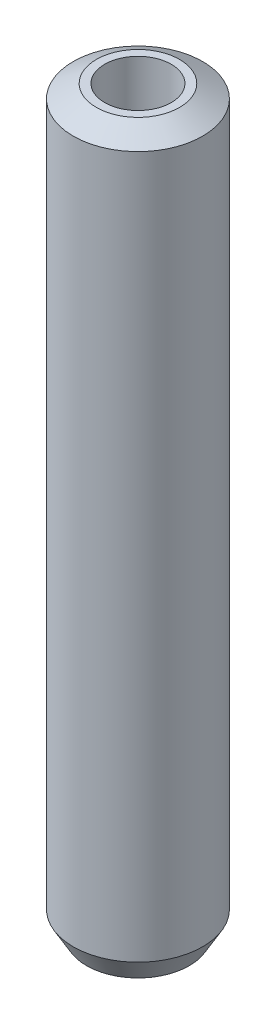
SolidWorks part; units mm, degrees
ref_plane "Front Plane" through (0, 0, 0) normal (0, 0, 1) x (1, 0, 0)
ref_plane "Top Plane" through (0, 0, 0) normal (0, 1, 0) x (1, 0, 0)
ref_plane "Right Plane" through (0, 0, 0) normal (1, 0, 0) x (0, 0, -1)
sketch "Sketch1" plane through (0, 0, 0) normal (0, 1, 0) x (1, 0, 0)
  circle A0 centre (0, 0) radius 20
  dimension "SHAFT_OD" = 40
extrude "Boss-Extrude1" add sketch "Sketch1" along normal blind 228.2709
sketch "Sketch2" plane through (0, 0, 0) normal (0, 1, 0) x (1, 0, 0)
  circle A0 centre (0, 0) radius 10.2807
  dimension "BORE_D" = 20.5614
extrude "Cut-Extrude1" cut sketch "Sketch2" along normal through all
chamfer "Chamfer1" distance 4.1214 angle 60 2 edges at (0, 228.2709, 20) (0, 0, 20) first distance on face at (0, 228.2709, 20) first distance on face at (0, 0, 10.2807)
